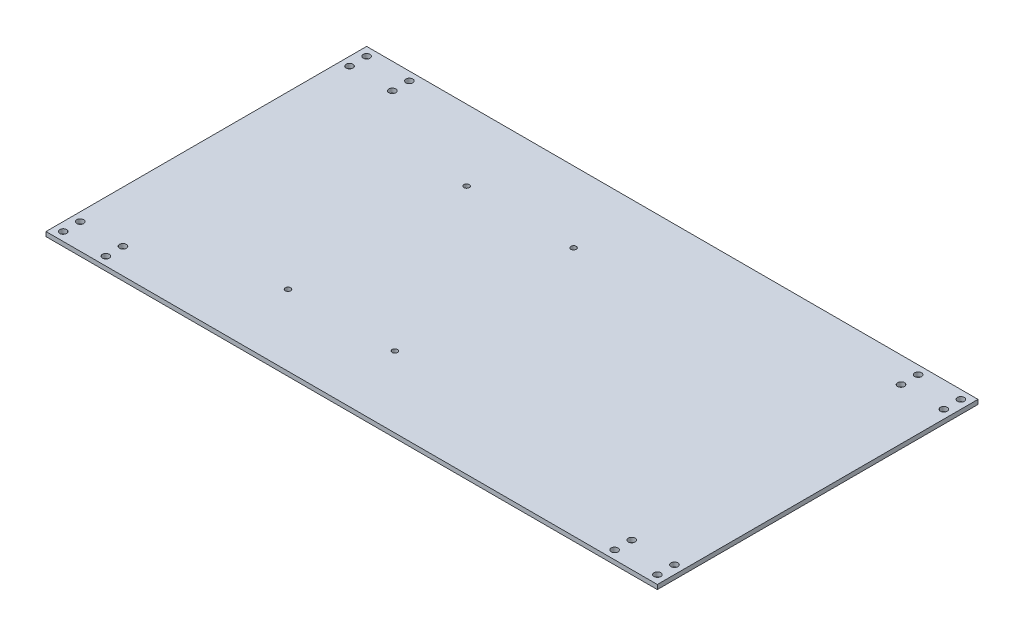
SolidWorks part; units mm, degrees
ref_plane "Płaszczyzna przednia" through (0, 0, 0) normal (0, 0, 1) x (1, 0, 0)
ref_plane "Płaszczyzna górna" through (0, 0, 0) normal (0, 1, 0) x (1, 0, 0)
ref_plane "Płaszczyzna prawa" through (0, 0, 0) normal (1, 0, 0) x (0, 0, -1)
sketch "Szkic1" plane through (0, 0, 0) normal (0, 1, 0) x (1, 0, 0)
  line L0 (-5.72, 0) -> (5.72, 0) construction
  line L1 (-715, -375) -> (715, -375)
  line L2 (-715, -375) -> (-715, 375)
  line L3 (-715, 375) -> (715, 375)
  line L4 (715, -375) -> (715, 375)
  line L6 (0, -5.72) -> (0, 5.72) construction
  point P4 (-715, 0)
  point P7 (0, 375)
  dimension "D1" = 1430
  dimension "D2" = 750
extrude "Dodanie-wyciągnięcie1" add sketch "Szkic1" along normal blind 10.4
sketch "Szkic2" plane through (0, 10.4, 0) normal (0, 1, 0) x (1, 0, 0)
  line L0 (715, -375) -> (715, 375) construction
  line L1 (-715, -375) -> (715, -375) construction
  line L2 (-5.72, 0) -> (5.72, 0) construction
  line L3 (0, -5.72) -> (0, 5.72) construction
  line L4 (-715, 375) -> (-715, -375) construction
  circle A0 centre (695, -355) radius 8
  circle A1 centre (695, -315) radius 8
  circle A2 centre (595, -355) radius 8
  circle A3 centre (595, -315) radius 8
  circle A4 centre (595, 315) radius 8
  circle A5 centre (595, 355) radius 8
  circle A6 centre (695, 315) radius 8
  circle A7 centre (695, 355) radius 8
  circle A8 centre (-695, 355) radius 8
  circle A9 centre (-695, 315) radius 8
  circle A10 centre (-595, 355) radius 8
  circle A11 centre (-595, 315) radius 8
  circle A12 centre (-595, -315) radius 8
  circle A13 centre (-595, -355) radius 8
  circle A14 centre (-695, -315) radius 8
  circle A15 centre (-695, -355) radius 8
  circle A16 centre (-315, -209) radius 6.25
  circle A17 centre (-65, -209) radius 6.25
  circle A18 centre (-65, 209) radius 6.25
  circle A19 centre (-315, 209) radius 6.25
  point P10 (0, 0)
  point P47 (0, 0)
  dimension "D3" = 16
  dimension "D7" = 12.5
  dimension "D1" = 100
  dimension "D2" = 40
  dimension "D4" = 20
  dimension "D5" = 20
  dimension "D6" = 400
  dimension "D8" = 209
  dimension "D9" = 250
extrude "Wytnij-wyciągnięcie1" cut sketch "Szkic2" against normal up to next
sketch "Szkic3" [suppressed] plane through (0, 10.4, 0) normal (0, 1, 0) x (1, 0, 0)
  line L1 (-715, -375) -> (85, -375)
  line L2 (-715, -375) -> (-715, 325)
  line L3 (-715, 325) -> (85, 325)
  line L4 (85, -375) -> (85, 325)
  line L5 (-878.942, 539.9844) -> (876.0073, 539.9844)
  line L6 (-878.942, 539.9844) -> (-878.942, -535.5824)
  line L7 (-878.942, -535.5824) -> (876.0073, -535.5824)
  line L8 (876.0073, 539.9844) -> (876.0073, -535.5824)
  dimension "D1" = 800
  dimension "D2" = 700
extrude "Wytnij-wyciągnięcie2" [suppressed] cut sketch "Szkic3" against normal blind 200
